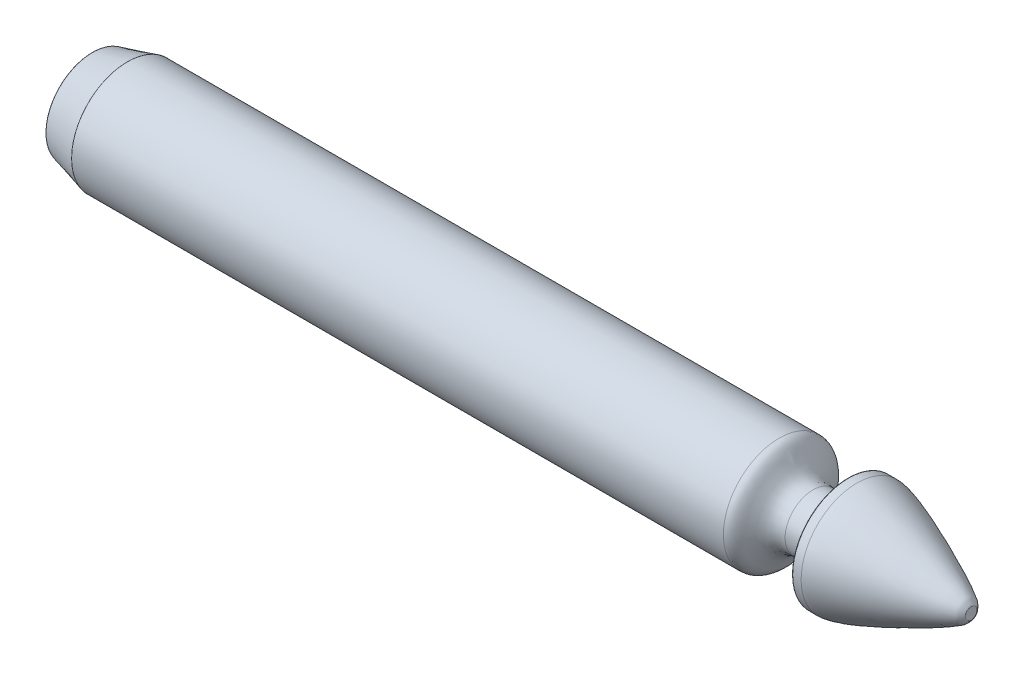
SolidWorks part; units mm, degrees
material "Stainless Steel (ferritic)"
ref_plane "Front" through (0, 0, 0) normal (0, 0, 1) x (1, 0, 0)
ref_plane "Top" through (0, 0, 0) normal (0, 1, 0) x (1, 0, 0)
ref_plane "Right" through (0, 0, 0) normal (1, 0, 0) x (0, 0, -1)
sketch "body_sketch" plane through (0, 0, 0) normal (0, 0, 1) x (1, 0, 0)
  line L1 (-16.7357, 3.175) -> (-10.9218, 3.175)
  line L2 (-48, 3.175) -> (-20.8111, 3.175)
  line L3 (-19.1074, 3.175) -> (-22.5343, 3.175) construction
  line L4 (-6.5, 3.175) -> (-7, 3.175)
  line L5 (-15.6683, 3.175) -> (-17.809, 3.175) construction
  line L6 (-50, 0) -> (-50, 2.6391)
  line L7 (-50, 2.6391) -> (-48, 3.175)
  line L9 (-7, 3.175) -> (-7, 1.5875)
  line L10 (-7, 1.5875) -> (-9, 1.5875)
  line L13 (14.3233, 1.5875) -> (12.3233, 1.5875) construction
  line L14 (-10.9218, 3.175) -> (-7, 3.175) construction
  line L15 (0, 0) -> (-50, 0)
  line L17 (0, 0.3278) -> (0, 0)
  spline S0 degree 3 poles (-6.5, 3.175) (-5.4841, 3.175) (-0.4543, 0.8964) (-0.0546, 0.4243) (0, 0.3773) (0, 0.3278) knots 0 0 0 0 0.586138 0.686138 1 1 1 1
  spline S1 degree 3 poles (-10.9218, 3.175) (-10.1654, 3.175) (-10.25, 1.5875) (-9, 1.5875) knots 0 0 0 0 1 1 1 1
  spline S2 degree 3 poles (-20.8111, 3.175) (-19.3832, 3.175) (-18.0736, 3.175) (-16.7357, 3.175) knots 0 0 0 0 1 1 1 1
  dimension "D1" = 3.175
  dimension "D2" = 0.5
  dimension "D3" = 2
  dimension "D4" = 1.5875
  dimension "D5" = 50
  dimension "D6" = 7
  dimension "D7" = 3.175
  dimension "D8" = 15
  dimension "D9" = 2
revolve "body" add sketch "body_sketch" angle 360 about L15
sketch "minimum_diameter" plane through (0, 0, 0) normal (1, 0, 0) x (0, 0, -1)
  circle A0 centre (0, 0) radius 1.5875 construction
  circle A2 centre (0, 0) radius 1.5875 construction
fillet "break_edges" radius 0.02 3 edges at (-50, 2.6391, 0) (-48, 3.175, 0) (-7, 3.175, 0)
